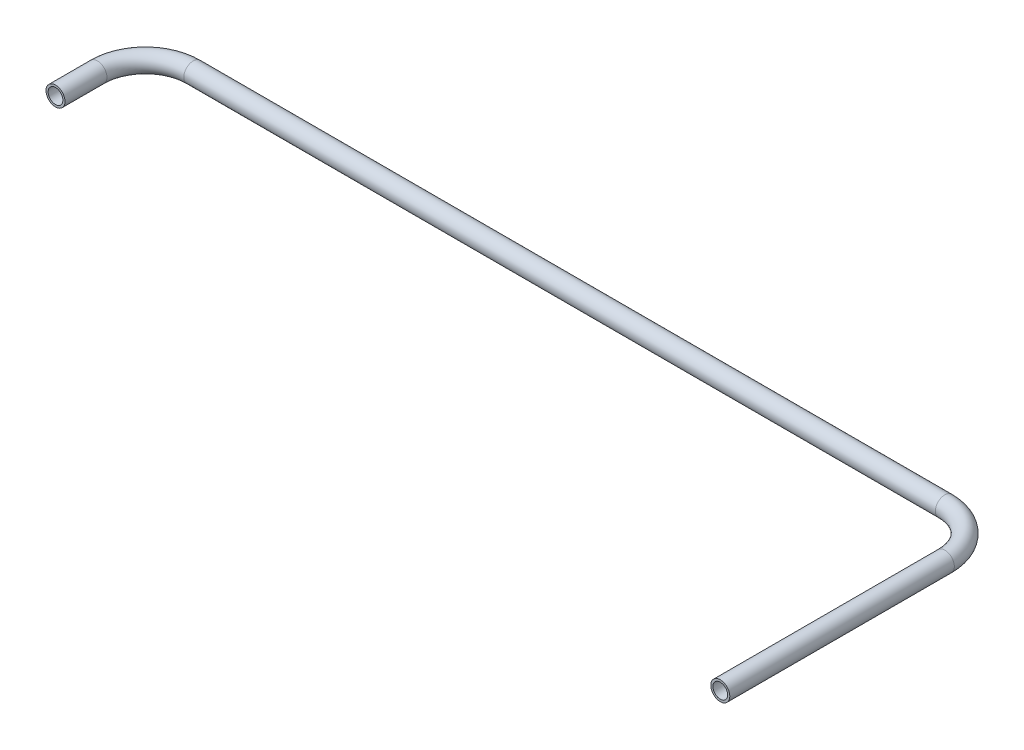
SolidWorks part; units mm, degrees
ref_plane "Front Plane" through (0, 0, 0) normal (0, 0, 1) x (1, 0, 0)
ref_plane "Top Plane" through (0, 0, 0) normal (0, 1, 0) x (1, 0, 0)
ref_plane "Right Plane" through (0, 0, 0) normal (1, 0, 0) x (0, 0, -1)
sketch "Sketch1" plane through (0, 0, 0) normal (0, 1, 0) x (1, 0, 0)
  line L0 (0, 0) -> (0, 14)
  line L1 (16, 30) -> (267, 30)
  line L2 (283, 14) -> (283, -61)
  arc A0 (267, 30) -> (283, 14) centre (267, 14) cw
  arc A1 (0, 14) -> (16, 30) centre (16, 14) cw
  dimension "D1" = 16
  dimension "D2" = 16
  dimension "D3" = 14
  dimension "D4" = 75
  dimension "D5" = 283
sketch "Sketch2" plane through (0, 0, 0) normal (0, 0, 1) x (1, 0, 0)
  circle A0 centre (0, 0) radius 3.175
  dimension "D1" = 6.35
sweep "Sweep-Thin1" add profiles "Sketch2" path "Sketch1" parameters "D1"=0.7112
